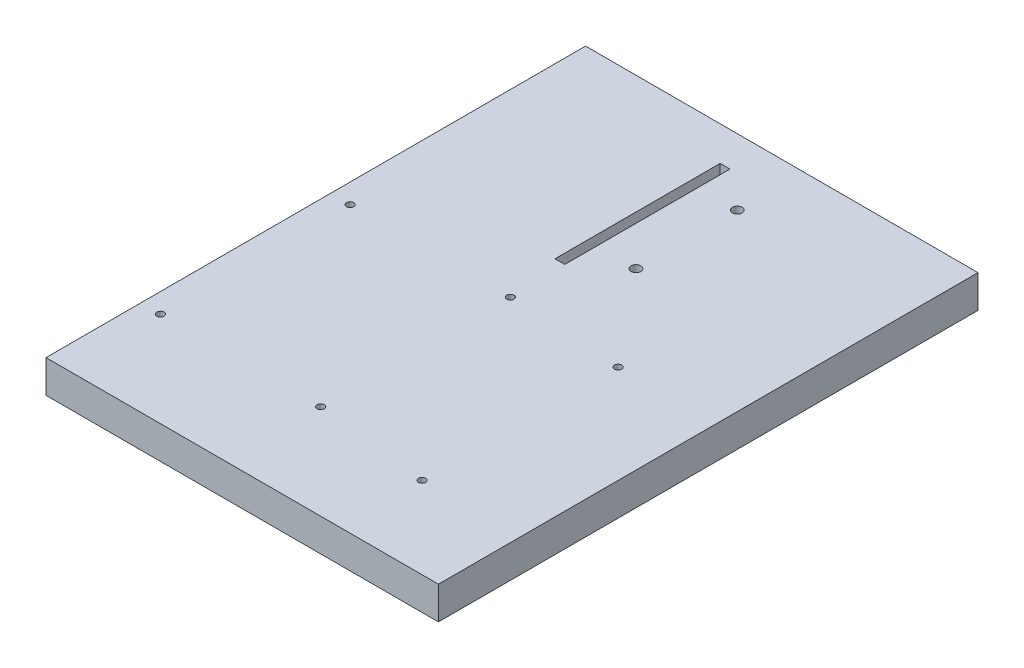
SolidWorks part; units mm, degrees
ref_plane "Front Plane" through (0, 0, 0) normal (0, 0, 1) x (1, 0, 0)
ref_plane "Top Plane" through (0, 0, 0) normal (0, 1, 0) x (1, 0, 0)
ref_plane "Right Plane" through (0, 0, 0) normal (1, 0, 0) x (0, 0, -1)
sketch "Sketch1" plane through (0, 0, 0) normal (0, 1, 0) x (1, 0, 0)
  line L1 (0, 0) -> (120, 0)
  line L2 (0, 0) -> (0, 165)
  line L3 (0, 165) -> (120, 165)
  line L4 (120, 0) -> (120, 165)
  dimension "D1" = 120
  dimension "D2" = 165
extrude "Base" add sketch "Sketch1" along normal blind 10
hole_wizard "Pi-MountHoles" positions "Sketch13" profile "Sketch14" counterbore size "M2" standard "ANSI Metric" end condition up to next
sketch "Sketch13" plane through (0, 0, 0) normal (0, -1, 0) x (-1, 0, 0)
  line L1 (0, 0) -> (-120, 0) construction
  line L2 (0, 165) -> (0, 0) construction
  point P0 (-6, 29)
  point P2 (-55, 29)
  point P4 (-55, 87)
  point P6 (-6, 87)
  dimension "D1" = 49
  dimension "D2" = 58
  dimension "D3" = 87
  dimension "D4" = 6
sketch "Sketch14" plane through (6, 0, -29) normal (1, 0, 0) x (0, 0, -1)
  line L0 (0, 0) -> (0, 10)
  line L1 (0, 10) -> (1.1, 10)
  line L3 (1.1, 10) -> (1.1, 1.6)
  line L4 (2.5, 1.6) -> (1.1, 1.6)
  line L5 (2.5, 1.6) -> (2.5, 0.025)
  line L6 (2.5, 0.025) -> (2.525, 0)
  line L7 (2.525, 0) -> (0, 0)
  line L8 (-2.5, 0.025) -> (-2.525, 0) construction
  line L11 (0, -6.35) -> (0, 107.95) construction
  dimension "Thru Hole Dia." = 2.2
  dimension "Thru Hole Depth" = 10
  dimension "C'Bore Dia." = 5
  dimension "C'Bore Depth" = 1.6
  dimension "Near C'Sink Dia." = 5.05
  dimension "Near C'Sink Angle" = 90
hole_wizard "Battery-MountHoles" positions "Sketch15" profile "Sketch16" counterbore size "M2" standard "ANSI Metric" end condition up to next
sketch "Sketch15" plane through (0, 0, 0) normal (0, -1, 0) x (-1, 0, 0)
  line L0 (0, 0) -> (-120, 0) construction
  circle A0 centre (-55, 87) radius 1.1 construction
  point P0 (-90, 25)
  point P2 (-90, 84.95)
  dimension "D1" = 59.95
  dimension "D2" = 25
  dimension "D3" = 35
sketch "Sketch16" plane through (90, 0, -25) normal (1, 0, 0) x (0, 0, -1)
  line L0 (0, 0) -> (0, 10)
  line L1 (0, 10) -> (1.1, 10)
  line L3 (1.1, 10) -> (1.1, 1.6)
  line L4 (2.5, 1.6) -> (1.1, 1.6)
  line L5 (2.5, 1.6) -> (2.5, 0.025)
  line L6 (2.5, 0.025) -> (2.525, 0)
  line L7 (2.525, 0) -> (0, 0)
  line L8 (-2.5, 0.025) -> (-2.525, 0) construction
  line L11 (0, -6.35) -> (0, 107.95) construction
  dimension "Thru Hole Dia." = 2.2
  dimension "Thru Hole Depth" = 10
  dimension "C'Bore Dia." = 5
  dimension "C'Bore Depth" = 1.6
  dimension "Near C'Sink Dia." = 5.05
  dimension "Near C'Sink Angle" = 90
sketch "Sketch17" plane through (0, 10, 0) normal (0, 1, 0) x (1, 0, 0)
  line L1 (51.65, 154.5) -> (54.65, 154.5)
  line L2 (51.65, 154.5) -> (51.65, 104)
  line L3 (51.65, 104) -> (54.65, 104)
  line L4 (54.65, 154.5) -> (54.65, 104)
  circle A4 centre (55, 87) radius 1.1 construction
  dimension "D1" = 3.35
  dimension "D4" = 17
  dimension "D2" = 3
  dimension "D3" = 50.5
extrude "StepperBracketSlot" cut sketch "Sketch17" against normal up to surface (10 mm away) up to face at (90, 0, -27.525)
sketch "Sketch18" plane through (0, 10, 0) normal (0, 1, 0) x (1, 0, 0)
  line L1 (54.65, 104) -> (54.65, 154.5) construction
  circle A0 centre (66.65, 144.75) radius 1.5
  circle A1 centre (66.65, 113.75) radius 1.5
  point P10 (54.65, 129.25)
  dimension "D1" = 3
  dimension "D2" = 31
  dimension "D3" = 15.5
  dimension "D4" = 12
extrude "AngleBracket-MountHoles" cut sketch "Sketch18" against normal up to surface (10 mm away) up to face at (53.15, 0, -129.25)
equation "\"D3@Sketch18\"=\"D2@Sketch18\"/2"
